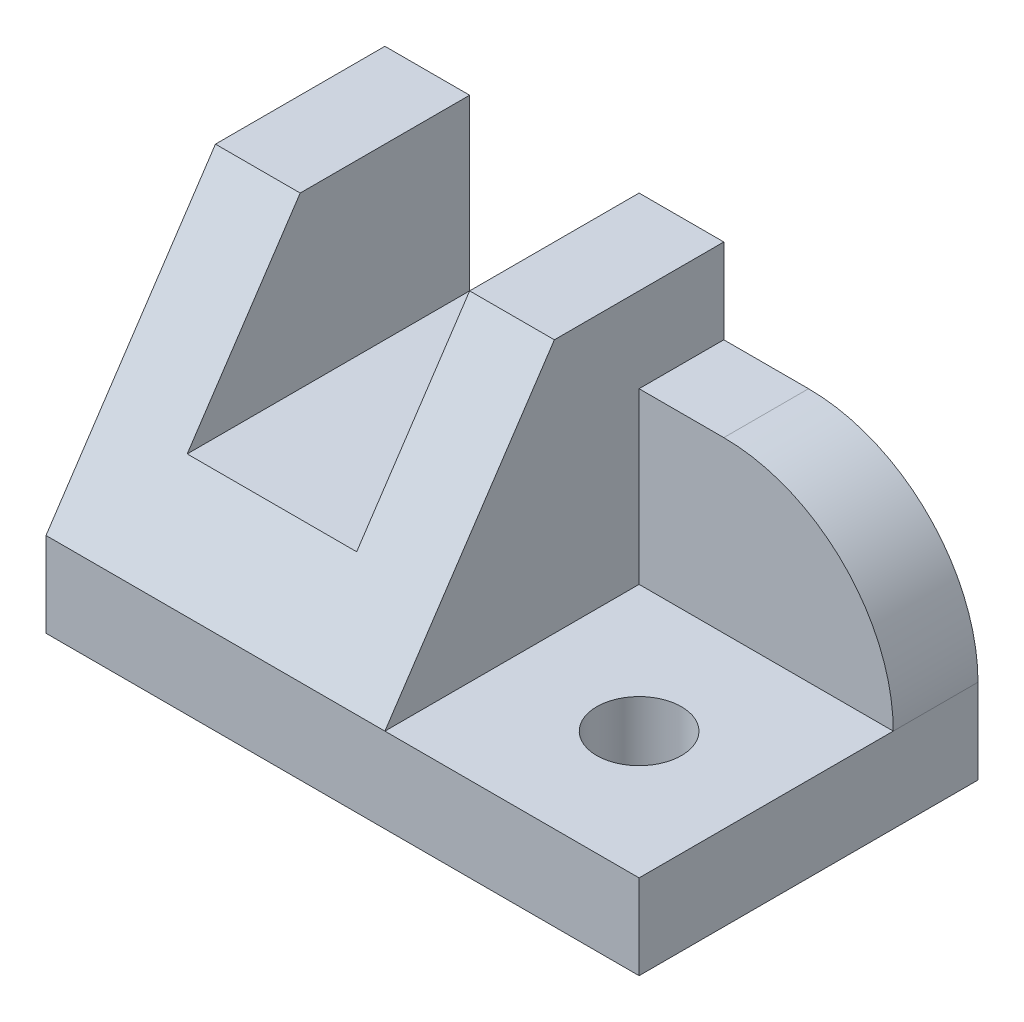
SolidWorks part; units mm, degrees
ref_plane "前基準面" through (0, 0, 0) normal (0, 0, 1) x (1, 0, 0)
ref_plane "上基準面" through (0, 0, 0) normal (0, 1, 0) x (1, 0, 0)
ref_plane "右基準面" through (0, 0, 0) normal (1, 0, 0) x (0, 0, -1)
sketch "草圖1" plane through (0, 0, 0) normal (0, 1, 0) x (1, 0, 0)
  line L1 (-17.5, -10) -> (17.5, -10)
  line L2 (-17.5, -10) -> (-17.5, 10)
  line L3 (-17.5, 10) -> (17.5, 10)
  line L4 (17.5, -10) -> (17.5, 10)
  line L5 (-17.5, -10) -> (17.5, 10) construction
  line L6 (-17.5, 10) -> (17.5, -10) construction
  line L7 (-17.5, 10) -> (2.5, 10)
  line L8 (-17.5, 10) -> (-17.5, -10)
  line L9 (-17.5, -10) -> (2.5, -10)
  line L10 (2.5, 10) -> (2.5, -10)
  line L11 (2.5, 10) -> (17.5, 10)
  line L12 (2.5, 10) -> (2.5, 5)
  line L13 (2.5, 5) -> (17.5, 5)
  line L14 (17.5, 10) -> (17.5, 5)
  circle A0 centre (10, -2.5) radius 2.5
  point P0 (0, 0)
  dimension "D5" = 5
  dimension "D1" = 35
  dimension "D2" = 20
  dimension "D3" = 5
  dimension "D4" = 20
  dimension "D6" = 7.5
  dimension "D7" = 7.5
extrude "填料-伸長1" add sketch "草圖1" along normal blind 5 contours L13 L10 L1 L4 A0 region at (2.7121, 0, 2.5)
extrude "填料-伸長2" add sketch "草圖1<3>" along normal blind 15 contours L10 L13 L4 L3 region at (10, 0, -7.5)
sketch "草圖1<3>" plane through (0, 0, 0) normal (0, 1, 0) x (1, 0, 0) same geometry as "草圖1"
extrude "填料-伸長3" add sketch "草圖1<4>" along normal blind 20 contours L10 L3 L2 L1 region at (-7.5, 0, 0)
sketch "草圖1<4>" plane through (0, 0, 0) normal (0, 1, 0) x (1, 0, 0) same geometry as "草圖1"
sketch "草圖2" plane through (2.5, 0, 0) normal (1, 0, 0) x (0, 0, -1)
  line L0 (-10, 5) -> (0, 20)
  line L1 (10, 20) -> (-10, 20) construction
  line L2 (0, 20) -> (-10, 20)
  line L3 (-10, 20) -> (-10, 5)
  dimension "D1" = 10
extrude "除料-伸長1" cut sketch "草圖2" against normal blind 20
sketch "草圖3" plane through (0, 0, -10) normal (0, 0, -1) x (-1, 0, 0)
  line L0 (17.5, 20) -> (-2.5, 20) construction
  line L1 (2.5, 20) -> (12.5, 20)
  line L2 (2.5, 20) -> (2.5, 10)
  line L3 (2.5, 10) -> (12.5, 10)
  line L4 (12.5, 20) -> (12.5, 10)
  line L5 (17.5, 20) -> (17.5, 0) construction
  line L6 (-2.5, 20) -> (-2.5, 15) construction
  dimension "D1" = 10
  dimension "D2" = 5
  dimension "D3" = 5
extrude "除料-伸長2" cut sketch "草圖3" against normal blind 20
fillet "圓角1" radius 10 1 edges at (17.5, 15, -7.5)
scale "縮放比例1" scale about centroid uniform scaling yes scale factor 0.2
